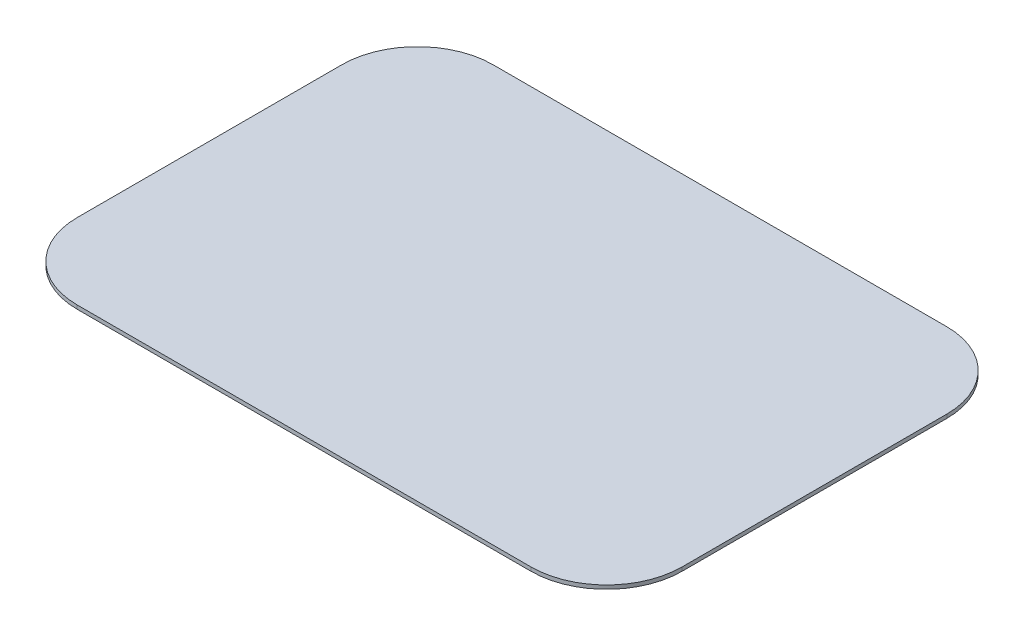
SolidWorks part; units mm, degrees
ref_plane "Front Plane" through (0, 0, 0) normal (0, 0, 1) x (1, 0, 0)
ref_plane "Top Plane" through (0, 0, 0) normal (0, 1, 0) x (1, 0, 0)
ref_plane "Right Plane" through (0, 0, 0) normal (1, 0, 0) x (0, 0, -1)
sketch "Sketch1" plane through (0, 0, 0) normal (0, 1, 0) x (1, 0, 0)
  line L1 (-80, -55) -> (80, -55)
  line L2 (-80, -55) -> (-80, 55)
  line L3 (-80, 55) -> (80, 55)
  line L4 (80, -55) -> (80, 55)
  line L5 (-80, -55) -> (80, 55) construction
  line L6 (-80, 55) -> (80, -55) construction
  point P0 (0, 0)
  dimension "D1" = 110
  dimension "D2" = 160
extrude "Boss-Extrude1" add sketch "Sketch1" against normal blind 1 contours L2 L1 L4 L3
fillet "Fillet1" radius 20 4 edges at (80, -0.5, -55) (80, -0.5, 55) (-80, -0.5, 55) (-80, -0.5, -55)
